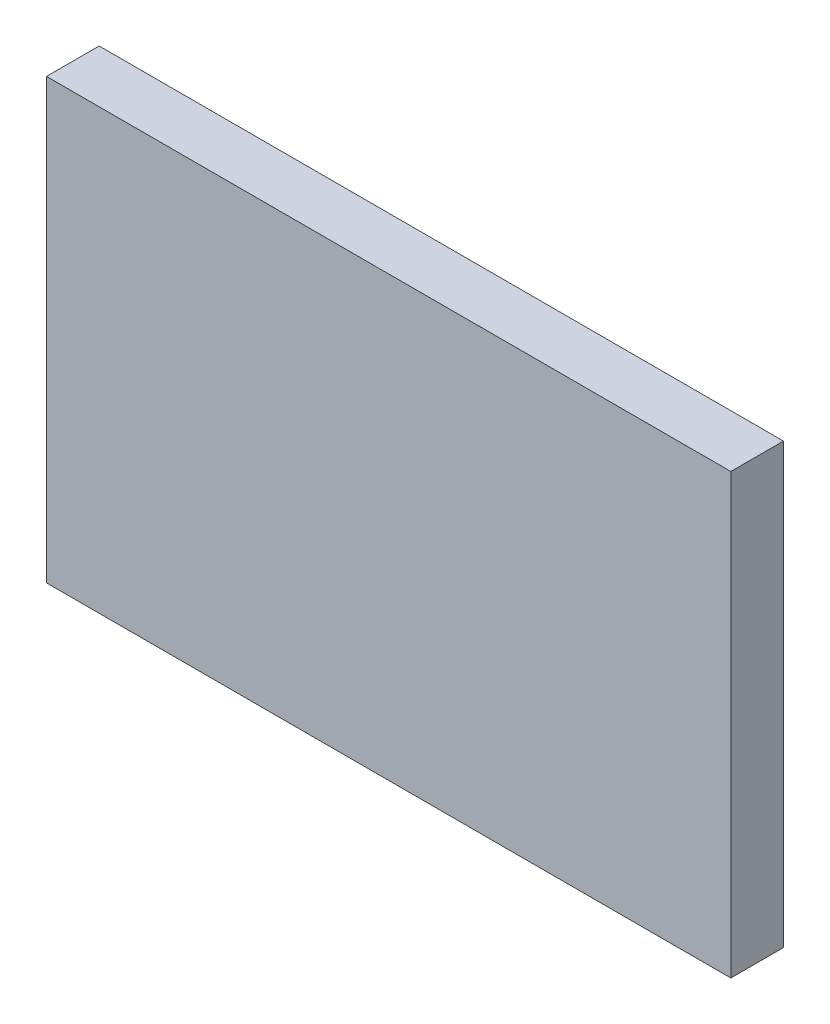
SolidWorks part; units mm, degrees
other "Magic Base"
ref_plane "Front Plane" through (0, 0, 0) normal (0, 0, 1) x (1, 0, 0)
ref_plane "Top Plane" through (0, 0, 0) normal (0, 1, 0) x (1, 0, 0)
ref_plane "Right Plane" through (0, 0, 0) normal (1, 0, 0) x (0, 0, -1)
sketch "Sketch1" plane through (0, 0, 0) normal (0, 0, 1) x (1, 0, 0)
  line L1 (-195, 125) -> (195, 125)
  line L2 (-195, 125) -> (-195, -125)
  line L3 (-195, -125) -> (195, -125)
  line L4 (195, 125) -> (195, -125)
  line L5 (-195, 125) -> (195, -125) construction
  line L6 (-195, -125) -> (195, 125) construction
  point P0 (0, 0)
  dimension "D1" = 390
  dimension "D2" = 250
extrude "Boss-Extrude1" add sketch "Sketch1" along normal blind 30
equation "\"boxWidth\"= 25cm"
equation "\"boxTall\"= 39cm"
equation "\"boxHeight\"= 3cm"
